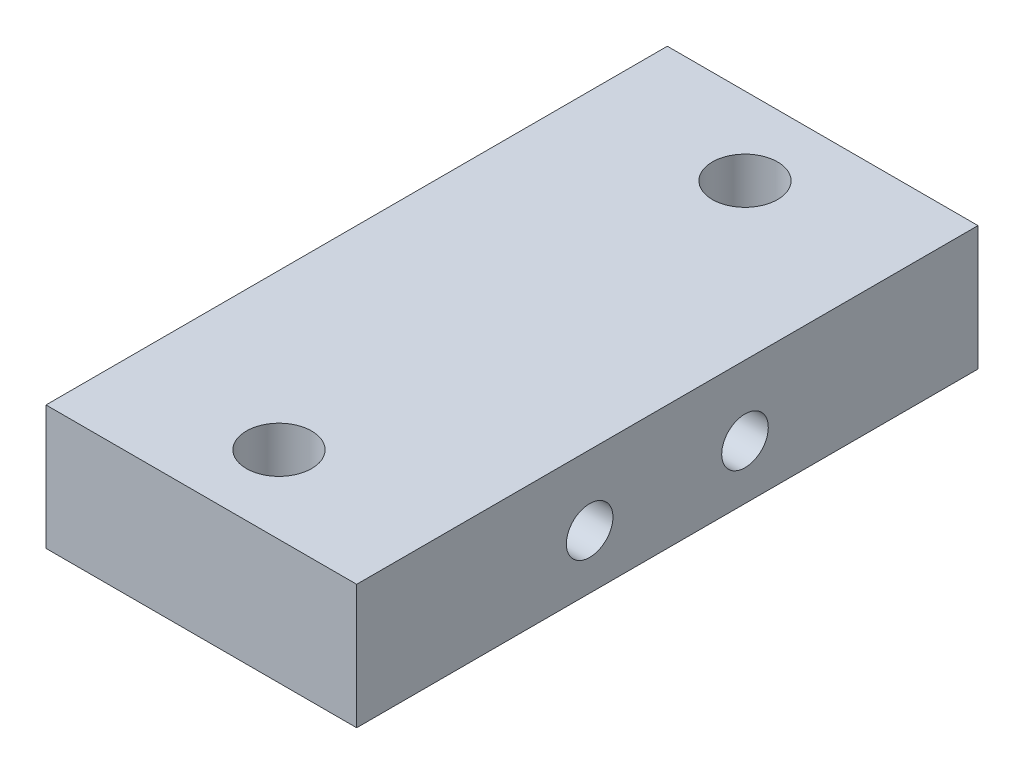
SolidWorks part; units mm, degrees
ref_plane "Front Plane" through (0, 0, 0) normal (0, 0, 1) x (1, 0, 0)
ref_plane "Top Plane" through (0, 0, 0) normal (0, 1, 0) x (1, 0, 0)
ref_plane "Right Plane" through (0, 0, 0) normal (1, 0, 0) x (0, 0, -1)
sketch "Sketch2" plane through (0, 33.7573, 0) normal (0, 1, 0) x (1, 0, 0)
  line L1 (-70, 10.5) -> (-90, 10.5)
  line L2 (-70, 10.5) -> (-70, 50.5)
  line L3 (-70, 50.5) -> (-90, 50.5)
  line L4 (-90, 10.5) -> (-90, 50.5)
extrude "Boss-Extrude2" add sketch "Sketch2" along normal blind 8
sketch "Sketch3" plane through (0, 41.7573, 0) normal (0, 1, 0) x (1, 0, 0)
  line L0 (-90, 20.5) -> (-70, 20.5) construction
  line L1 (-90, 20.5) -> (-70, 20.5) construction
  line L2 (-90, 40.5) -> (-70, 40.5) construction
  line L3 (-90, 40.5) -> (-70, 40.5) construction
  line L4 (-80, 40.5) -> (-80, 50.5) construction
  line L5 (-70, 50.5) -> (-90, 50.5) construction
  line L6 (-80, 20.5) -> (-80, 10.5) construction
  line L7 (-90, 10.5) -> (-70, 10.5) construction
  circle A0 centre (-80, 15.5) radius 2.1
  circle A1 centre (-80, 45.5) radius 2.1
extrude "Cut-Extrude1" cut sketch "Sketch3" against normal up to surface (8 mm away) up to face at (-80, 33.7573, -30.5)
sketch "Sketch4" plane through (-70, 0, 0) normal (1, 0, 0) x (0, 0, -1)
  circle A0 centre (25.5, 37.2573) radius 1.5
  circle A1 centre (35.5, 37.2573) radius 1.5
extrude "Cut-Extrude2" cut sketch "Sketch4" against normal blind 15 contours A1 | A0
